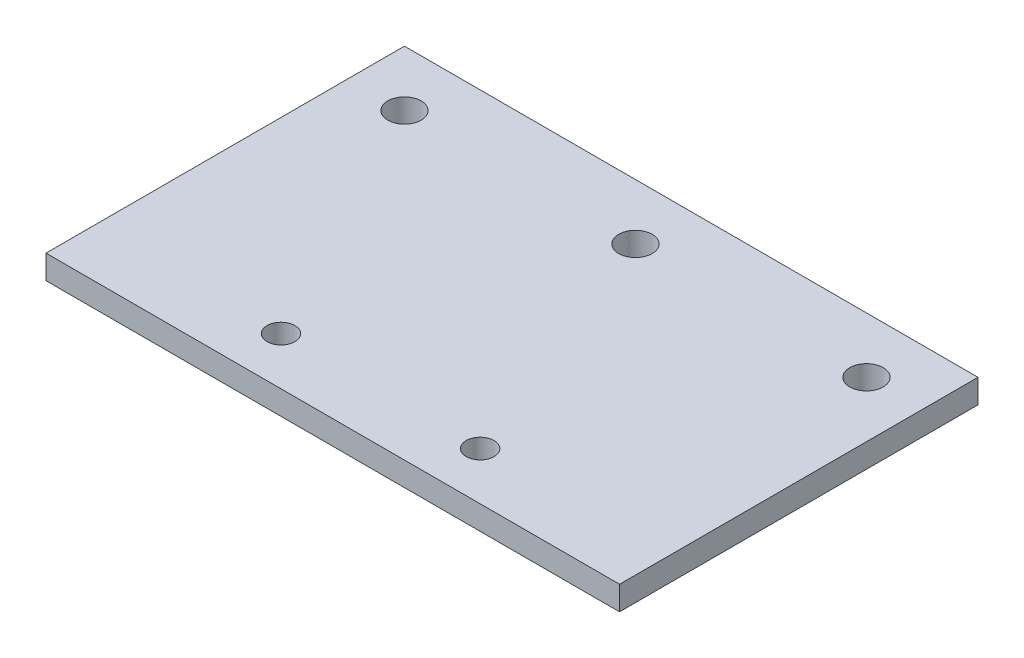
SolidWorks part; units mm, degrees
material "Acrylic (Medium-high impact)"
ref_plane "Front Plane" through (0, 0, 0) normal (0, 0, 1) x (1, 0, 0)
ref_plane "Top Plane" through (0, 0, 0) normal (0, 1, 0) x (1, 0, 0)
ref_plane "Right Plane" through (0, 0, 0) normal (1, 0, 0) x (0, 0, -1)
sketch "Sketch1" plane through (0, 0, 0) normal (0, 1, 0) x (1, 0, 0)
  line L0 (0, 0) -> (72, 0)
  line L1 (72, 0) -> (72, -45)
  line L2 (72, -45) -> (0, -45)
  line L3 (0, -45) -> (0, 0)
  circle A0 centre (7, -7) radius 2.1
  circle A1 centre (36, -7) radius 2.1
  circle A2 centre (65, -7) radius 2.1
  circle A3 centre (23.5, -39) radius 1.75
  circle A4 centre (48.5, -39) radius 1.75
  circle A5 centre (23.5, -39) radius 1.75 construction
  circle A6 centre (48.5, -39) radius 1.75 construction
  dimension "D3" = 4.2
  dimension "D4" = 7
  dimension "D1" = 72
  dimension "D2" = 45
  dimension "D5" = 29
  dimension "D6" = 7
  dimension "D7" = 7
extrude "Boss-Extrude1" add sketch "Sketch1" along normal blind 3
sketch "Sketch2" plane through (0, 0, 0) normal (0, -1, 0) x (1, 0, 0)
  line L0 (2.8767, 45) -> (2.8767, 0) construction
  line L1 (0, 45) -> (72, 45) construction
  line L2 (72, 0) -> (0, 0) construction
  text T0 "group 3" font "Century Gothic" height in points 8
extrude "Cut-Extrude2" cut sketch "Sketch2" against normal blind 0.5
